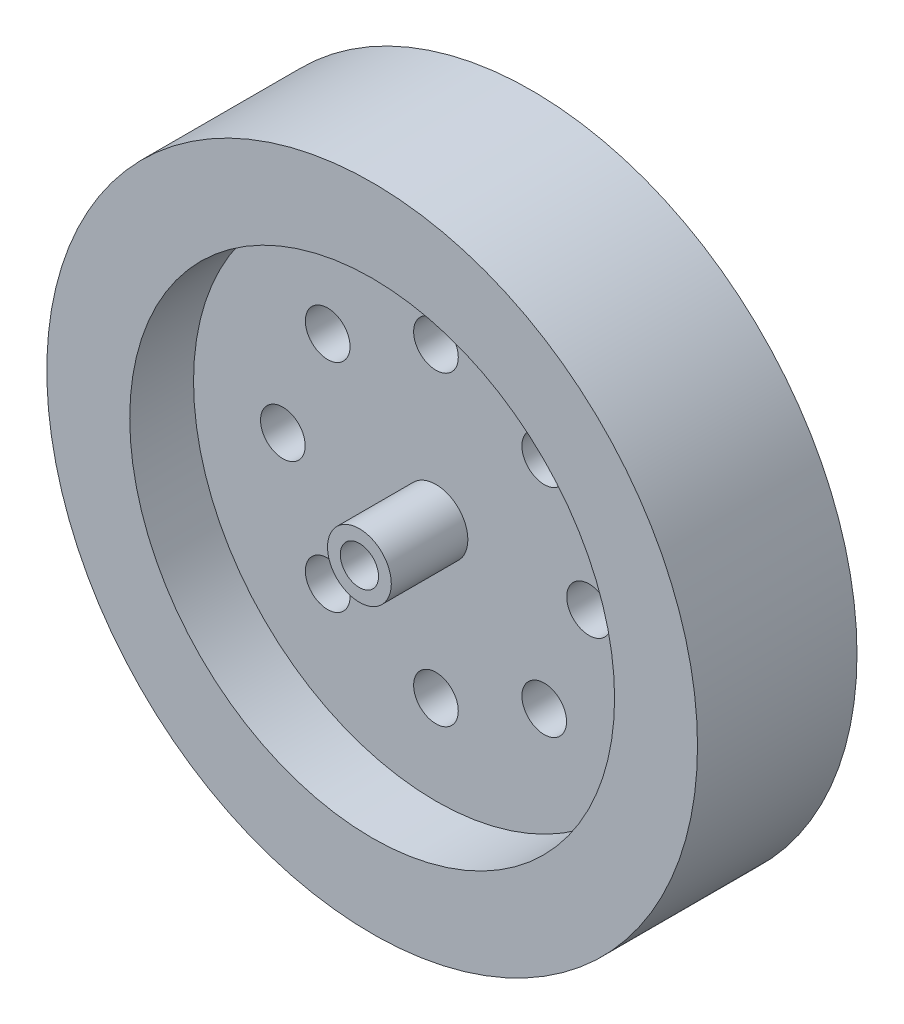
SolidWorks part; units mm, degrees
ref_plane "정면" through (0, 0, 0) normal (0, 0, 1) x (1, 0, 0)
ref_plane "윗면" through (0, 0, 0) normal (0, 1, 0) x (1, 0, 0)
ref_plane "우측면" through (0, 0, 0) normal (1, 0, 0) x (0, 0, -1)
sketch "스케치1" plane through (0, 0, 0) normal (0, 0, 1) x (1, 0, 0)
  circle A0 centre (0, 0) radius 51
  circle A1 centre (0, 0) radius 24 construction
  circle A2 centre (0, 0) radius 38
  circle A3 centre (0, 0) radius 3
  circle A4 centre (0, 24) radius 3.5
  circle A5 centre (16.9706, 16.9706) radius 3.5
  circle A6 centre (24, 0) radius 3.5
  circle A7 centre (16.9706, -16.9706) radius 3.5
  circle A8 centre (0, -24) radius 3.5
  circle A9 centre (-16.9706, -16.9706) radius 3.5
  circle A10 centre (-24, 0) radius 3.5
  circle A11 centre (-16.9706, 16.9706) radius 3.5
  point P25 (0, 0)
  dimension "D1" = 102
  dimension "D2" = 48
  dimension "D3" = 13
  dimension "D4" = 6
  dimension "D5" = 7
  dimension "D6" = 8
extrude "보스-돌출1" add sketch "스케치1" against normal blind 25 contours A0
extrude "컷-돌출1" cut sketch "스케치1<3>" against normal blind 25 contours A8 | A11 | A4 | A5 | A6 | A7 | A8 | A9 | A10 | A3 region at (0, -24, 0)
sketch "스케치1<3>" plane through (0, 0, 0) normal (0, 0, 1) x (1, 0, 0) same geometry as "스케치1"
extrude "컷-돌출2" cut sketch "스케치1<4>" against normal blind 10 contours A2
sketch "스케치1<4>" plane through (0, 0, 0) normal (0, 0, 1) x (1, 0, 0) same geometry as "스케치1"
extrude "컷-돌출3" cut sketch "스케치1<5>" along normal blind 10 from surface contours A2 starting at face at (3.5, -24, -25)
sketch "스케치1<5>" plane through (0, 0, 0) normal (0, 0, 1) x (1, 0, 0) same geometry as "스케치1"
sketch "스케치2" plane through (0, 0, -10) normal (0, 0, 1) x (1, 0, 0)
  circle A0 centre (0, 0) radius 5
  circle A1 centre (0, 0) radius 3
  circle M3 centre (0, 0) radius 3
  dimension "D1" = 10
  dimension "D2" = 6
extrude "보스-돌출2" add sketch "스케치2" along normal blind 12 contours A0 M3 region at (-4.8586, 0, -10)
